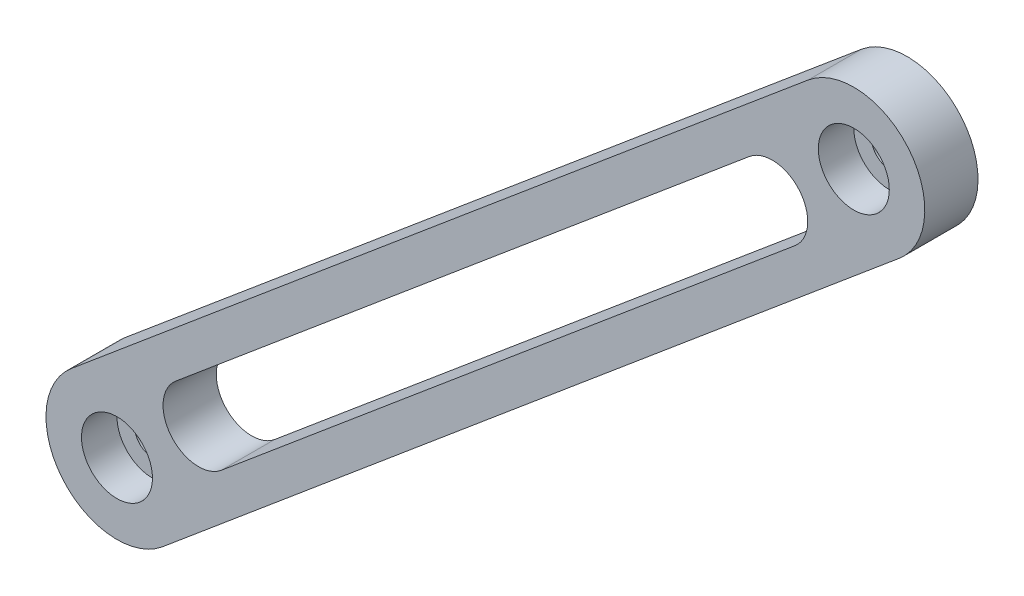
SolidWorks part; units mm, degrees
ref_plane "Front Plane" through (0, 0, 0) normal (0, 0, 1) x (1, 0, 0)
ref_plane "Top Plane" through (0, 0, 0) normal (0, 1, 0) x (1, 0, 0)
ref_plane "Right Plane" through (0, 0, 0) normal (1, 0, 0) x (0, 0, -1)
sketch "Sketch1" plane through (0, 0, 0) normal (0, 0, 1) x (1, 0, 0)
  line L0 (0, 0) -> (179.8502, 0) construction
  line L1 (8.1025, 0) -> (604.1295, 500.126) construction
  line L2 (604.1295, 500.126) -> (692.3152, 0) construction
  line L5 (568.3452, 503.2567) -> (304.6956, 282.0285)
  line L7 (600.9988, 464.3417) -> (337.3493, 243.1135)
  line L9 (555.4857, 459.309) -> (350.2087, 287.0612) construction
  line L10 (563.6491, 449.5802) -> (358.3721, 277.3324)
  line L11 (547.3223, 469.0378) -> (342.0453, 296.79)
  line L12 (321.0224, 262.571) -> (304.6956, 282.0285) construction
  line L13 (321.0224, 262.571) -> (337.3493, 243.1135) construction
  line L14 (568.3452, 503.2567) -> (600.9988, 464.3417) construction
  arc A0 (563.6491, 449.5802) -> (547.3223, 469.0378) centre (555.4857, 459.309) ccw
  arc A1 (342.0453, 296.79) -> (358.3721, 277.3324) centre (350.2087, 287.0612) ccw
  circle A2 centre (321.0224, 262.571) radius 6.35
  arc A3 (304.6956, 282.0285) -> (337.3493, 243.1135) centre (321.0225, 262.571) ccw
  circle A4 centre (584.672, 483.7992) radius 6.35
  arc A5 (568.3452, 503.2567) -> (600.9988, 464.3417) centre (584.672, 483.7992) cw
  point P4 (0, 0)
  point P6 (0, 0)
  point P12 (452.8472, 373.1851)
  point P24 (584.672, 483.7992)
  dimension "D6" = 12.7
  dimension "D7" = 12.7
  dimension "D4" = 25.4
  dimension "D3" = 25.4
  dimension "D1" = 40
  dimension "D2" = 80
  dimension "D5" = 267.97
  dimension "D8" = 38.1
  dimension "D9" = 38.1
extrude "Boss-Extrude1" add sketch "Sketch1" along normal blind 19.05
sketch "Sketch2" plane through (0, 0, 19.05) normal (0, 0, 1) x (1, 0, 0)
  circle A0 centre (321.0224, 262.571) radius 12.7
  circle A1 centre (584.672, 483.7992) radius 12.7
  dimension "D1" = 25.4
extrude "Cut-Extrude1" cut sketch "Sketch2" against normal blind 12.7
